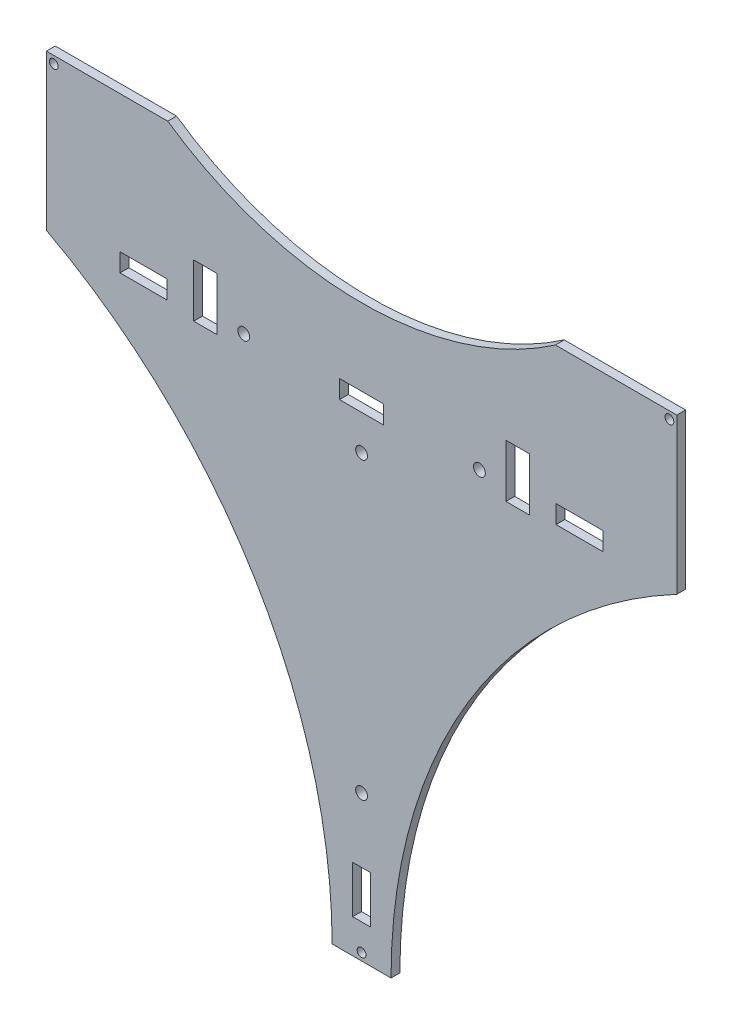
SolidWorks part; units mm, degrees
material "Oak"
ref_plane "Front Plane" through (0, 0, 0) normal (0, 0, 1) x (1, 0, 0)
ref_plane "Top Plane" through (0, 0, 0) normal (0, 1, 0) x (1, 0, 0)
ref_plane "Right Plane" through (0, 0, 0) normal (1, 0, 0) x (0, 0, -1)
sketch "Sketch1" plane through (0, 0, 0) normal (0, 0, 1) x (1, 0, 0)
  line L0 (-66, 54.3) -> (66, 54.3) construction
  line L1 (0, 54.3) -> (0, 0) construction
  line L2 (86.2011, 107) -> (107, 107)
  line L3 (53, 52.6) -> (53, 70.6) construction
  line L4 (57, 52.6) -> (49, 52.6)
  line L5 (57, 52.6) -> (57, 70.6)
  line L6 (0, -79.5) -> (0, -116.5) construction
  line L7 (-10, -107) -> (10, -107)
  line L8 (-107, 54.3) -> (-107, 107)
  line L9 (-107, 107) -> (-91.7989, 107)
  line L10 (107, 54.3) -> (107, 107)
  line L11 (-107, -107) -> (107, 107) construction
  line L12 (-107, 107) -> (107, -107) construction
  line L13 (-82, 60.5) -> (-66, 60.5)
  line L14 (-82, 60.5) -> (-82, 54.3)
  line L15 (-82, 54.3) -> (-66, 54.3)
  line L16 (-66, 60.5) -> (-66, 54.3)
  line L17 (82, 60.5) -> (66, 60.5)
  line L18 (82, 60.5) -> (82, 54.3)
  line L19 (82, 54.3) -> (66, 54.3)
  line L20 (66, 60.5) -> (66, 54.3)
  line L21 (-3.05, -95.5) -> (3.05, -95.5)
  line L22 (-3.05, -95.5) -> (-3.05, -79.5)
  line L23 (-3.05, -79.5) -> (3.05, -79.5)
  line L24 (3.05, -95.5) -> (3.05, -79.5)
  line L25 (57, 70.6) -> (49, 70.6)
  line L26 (49, 52.6) -> (49, 70.6)
  line L27 (-57, 52.6) -> (-49, 52.6)
  line L28 (-57, 52.6) -> (-57, 70.6)
  line L29 (-57, 70.6) -> (-49, 70.6)
  line L30 (-49, 52.6) -> (-49, 70.6)
  line L31 (-53, 52.6) -> (-53, 70.6) construction
  line L32 (65.8067, 107) -> (86.2011, 107)
  line L33 (-7.5, 54.3) -> (7.5, 54.3)
  line L34 (-7.5, 54.3) -> (-7.5, 60.5)
  line L35 (-7.5, 60.5) -> (7.5, 60.5)
  line L36 (7.5, 54.3) -> (7.5, 60.5)
  line L37 (-40, 57.4) -> (40, 57.4) construction
  line L38 (0, 54.3) -> (0, 60.5) construction
  line L40 (-91.7989, 107) -> (-65.8067, 107)
  circle A0 centre (-104.5, 104.5) radius 1.5
  circle A1 centre (104.5, 104.5) radius 1.5
  arc A2 (-65.8067, 107) -> (65.8067, 107) centre (0, 202.3724) ccw
  circle A3 centre (-40, 57.4) radius 2
  circle A4 centre (0, 104.5) radius 1.5 construction
  circle A6 centre (0, 42.4) radius 2
  circle A7 centre (0, -104.5) radius 1.5
  circle A9 centre (0, -57.6) radius 2
  circle A10 centre (40, 57.4) radius 2
  circle A11 centre (-104.5, 0) radius 1.5 [skipped]
  arc A12 (-10, -107) -> (-107, 54.3) centre (-192.6118, -107) ccw
  arc A13 (10, -107) -> (107, 54.3) centre (192.6118, -107) cw
  circle A14 centre (104.5, -104.5) radius 1.5 [skipped]
  circle A15 centre (-104.5, -104.5) radius 1.5 [skipped]
  circle A16 centre (104.5, 0) radius 1.5 [skipped]
  point P36 (0, 86.5)
  point P69 (0, 57.4)
  dimension "D4" = 3
  dimension "D16" = 20.5
  dimension "D23" = 40
  dimension "D10" = 4
  dimension "D11" = 100
  dimension "D3" = 214
  dimension "D5" = 209
  dimension "D6" = 6.2
  dimension "D7" = 16
  dimension "D8" = 46.5
  dimension "D9" = 156
  dimension "D12" = 20
  dimension "D13" = 4
  dimension "D14" = 15
  dimension "D15" = 214
  dimension "D17" = 82
  dimension "D18" = 8
  dimension "D20" = 18
  dimension "D21" = 15
  dimension "D22" = 6.1
extrude "Boss-Extrude1" add sketch "Sketch1" along normal blind 3
equation "\"bed-plate-thickness\"=3"
equation "\"D1@Boss-Extrude1\"=\"bed-plate-thickness\""
equation "\"D22@Sketch1\"=\"y-cross-rib-thickness\"+0.1"
equation "\"D6@Sketch1\"=\"y-rib-thickness\"+0.2"
equation "\"y-cross-rib-thickness\"=6"
equation "\"y-rib-thickness\"=6"
equation "\"x-plate-thickness\"=5"
equation "\"rod-diameter\"=12"
equation "\"t-nut-hole-diameter\"=3"
